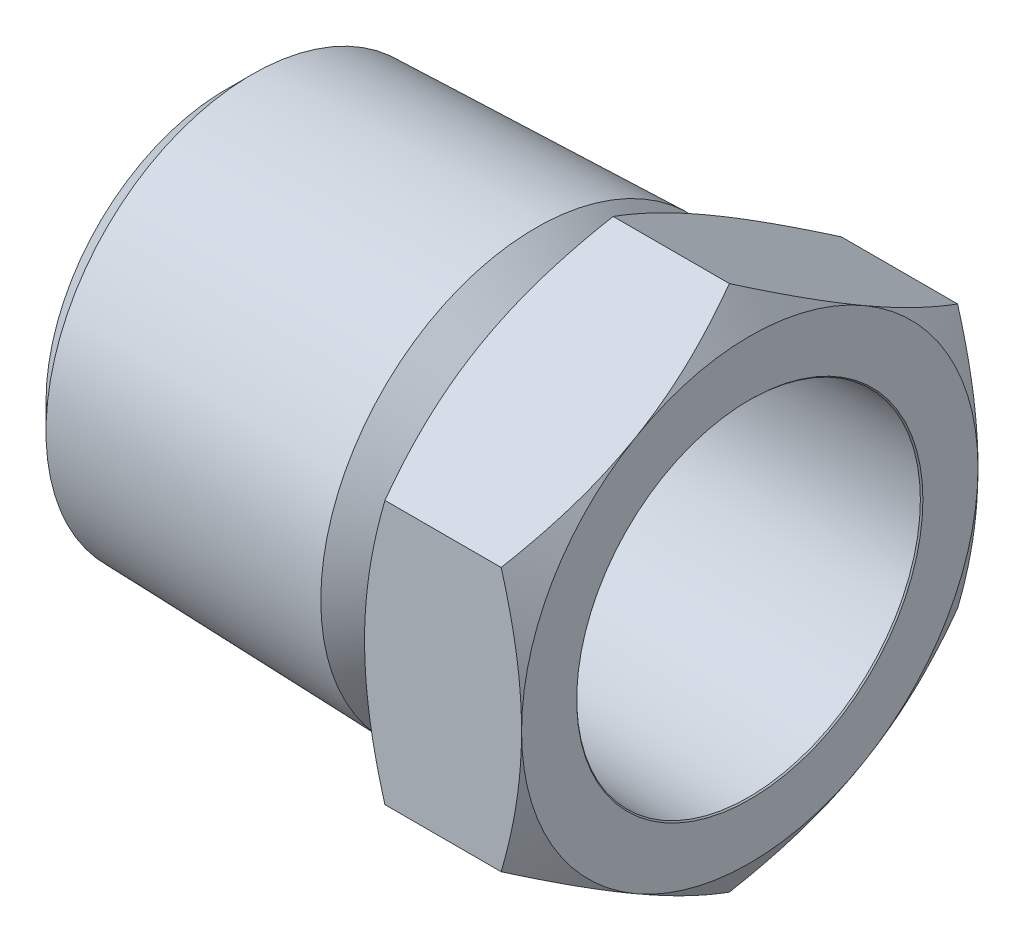
SolidWorks part; units mm, degrees
ref_plane "Front" through (0, 0, 0) normal (0, 0, 1) x (1, 0, 0)
ref_plane "Top" through (0, 0, 0) normal (0, 1, 0) x (1, 0, 0)
ref_plane "Right" through (0, 0, 0) normal (1, 0, 0) x (0, 0, -1)
sketch "Sketch1" plane through (0, 0, 0) normal (0, 0, 1) x (1, 0, 0)
  line L0 (-10.922, 0) -> (10.922, 0) construction
ref_plane "Plane1" through (-10.922, 0, 0) normal (1, 0, 0) x (0, 0, -1)
sketch "Sketch2" plane through (-10.922, 0, 0) normal (1, 0, 0) x (0, 0, -1)
  circle A0 centre (0, 0) radius 8.5725
  dimension "OD" = 17.145
extrude "Extrude1" add sketch "Sketch2" along normal up to vertex (21.844 mm away) draft 1.783 up to point (10.922, 0, 0) draft outward yes
sketch "Sketch3" plane through (-10.922, 0, 0) normal (-1, 0, 0) x (0, 0, 1)
  circle A1 centre (0, 0) radius 8.5725
  circle A2 centre (0, 0) radius 8.5725
  dimension "D1" = 0
curve "Helix/Spiral1" parameters "pitch"=1.4111
sketch "Sketch4" plane through (0, 0, 0) normal (0, 0, 1) x (1, 0, 0)
  line L0 (-12.1567, 8.5725) -> (-11.6276, 7.656)
  line L1 (-11.6276, 7.656) -> (-11.4512, 7.656)
  line L2 (-11.4512, 7.656) -> (-10.922, 8.5725)
  line L3 (-12.1567, 8.5725) -> (-10.922, 8.5725) construction
  line L4 (-11.8921, 8.1142) -> (-11.1866, 8.1142) construction
  line L5 (-11.5394, 7.656) -> (-11.5394, 8.5725) construction
  line L6 (-12.1567, 8.5725) -> (-10.7821, 8.8149)
  line L7 (-10.922, 8.5725) -> (-10.7821, 8.8149)
  line L8 (-10.922, 8.5725) -> (-10.922, -8.5725) construction
  dimension "D1" = 10
  dimension "D2" = 0.1764
  dimension "D3" = 0.7056
  dimension "D4" = 60
sweep "Cut-Sweep1" [suppressed] cut profiles "Sketch4" path "Helix/Spiral1"
sketch "Sketch5" plane through (-10.922, 0, 0) normal (1, 0, 0) x (0, 0, -1)
  circle A0 centre (0, 0) radius 7.656 construction
  circle A1 centre (0, 0) radius 7.529
  dimension "D1" = 0.127
extrude "Cut-Extrude1" cut sketch "Sketch5" along normal through all draft 45 flip side to cut
ref_plane "Plane2" through (10.922, 0, 0) normal (1, 0, 0) x (0, 0, -1)
ref_plane "Plane3" through (4.3688, 0, 0) normal (1, 0, 0) x (0, 0, -1)
sketch "Sketch8" plane through (4.3688, 0, 0) normal (1, 0, 0) x (0, 0, -1)
  circle A2 centre (0, 0) radius 14.9225
  circle A3 centre (0, 0) radius 14.9225
  dimension "D1" = 6.35
extrude "Cut-Extrude4" cut sketch "Sketch8" along normal through all
sketch "Sketch9" plane through (4.3688, 0, 0) normal (1, 0, 0) x (0, 0, -1)
  circle A0 centre (0, 0) radius 8.5725 construction
  circle A2 centre (0, 0) radius 7.656
extrude "Cut-Extrude5" cut sketch "Sketch9" against normal blind 1.0583 flip side to cut
ref_plane "Plane4" through (3.3105, 0, 0) normal (1, 0, 0) x (0, 0, -1)
sketch "Sketch10" plane through (3.3105, 0, 0) normal (1, 0, 0) x (0, 0, -1)
  circle A1 centre (0, 0) radius 7.656
  circle A2 centre (0, 0) radius 7.656
  dimension "D1" = 0
extrude "Cut-Extrude6" cut sketch "Sketch10" against normal through all draft 45 flip side to cut
sketch "Sketch6" plane through (10.922, 0, 0) normal (1, 0, 0) x (0, 0, -1)
  line L1 (0, 10.9985) -> (-9.525, 5.4993)
  line L2 (-9.525, 5.4993) -> (-9.525, -5.4993)
  line L3 (-9.525, -5.4993) -> (0, -10.9985)
  line L4 (0, -10.9985) -> (9.525, -5.4993)
  line L5 (9.525, -5.4993) -> (9.525, 5.4993)
  line L6 (9.525, 5.4993) -> (0, 10.9985)
  circle A0 centre (0, 0) radius 9.525 construction
  dimension "Hex" = 19.05
extrude "Extrude2" add sketch "Sketch6" against normal blind 6.5532
sketch "Sketch7" plane through (10.922, 0, 0) normal (1, 0, 0) x (0, 0, -1)
  line L0 (0, 10.9985) -> (-9.525, 5.4993) construction
  circle A0 centre (0, 0) radius 9.525
extrude "Cut-Extrude2" cut sketch "Sketch7" against normal through all draft 60 flip side to cut
sketch "Sketch18" plane through (4.3688, 0, 0) normal (-1, 0, 0) x (0, 0, 1)
  circle A0 centre (0, 0) radius 9.525 construction
  circle A1 centre (0, 0) radius 9.525
extrude "Extrude3" cut sketch "Sketch18" against normal blind 10 draft 60 flip side to cut
ref_plane "Plane5" through (0.762, 0, 0) normal (1, 0, 0) x (0, 0, -1)
sketch "Sketch11" plane through (0.762, 0, 0) normal (1, 0, 0) x (0, 0, -1)
  circle A0 centre (0, 0) radius 6.858
  dimension "OD2" = 13.716
extrude "Cut-Extrude7" cut sketch "Sketch11" along normal through all draft 1.783 draft outward yes
sketch "Sketch12" plane through (0.762, 0, 0) normal (1, 0, 0) x (0, 0, -1)
  circle A0 centre (0, 0) radius 6.858 construction
  circle A1 centre (0, 0) radius 6.858
curve "Helix/Spiral2" parameters "pitch 2"=1.4111
sketch "Sketch16" plane through (10.922, 0, 0) normal (1, 0, 0) x (0, 0, -1)
  circle A2 centre (0, 0) radius 7.2251
  circle A3 centre (0, 0) radius 7.2251
  dimension "D1" = 0.0508
sketch "Sketch14" plane through (0, 0, 0) normal (0, 0, 1) x (1, 0, 0)
  line L0 (-0.4727, 6.858) -> (0.762, 6.858) construction
  line L1 (0.762, 6.858) -> (0.2328, 5.9415) construction
  line L2 (0.2328, 5.9415) -> (0.0564, 5.9415)
  line L3 (0.0564, 5.9415) -> (-0.4727, 6.858)
  line L4 (-0.2081, 6.3997) -> (0.4974, 6.3997) construction
  line L5 (0.1446, 5.9415) -> (0.1446, 6.858) construction
  line L6 (-0.4727, 6.858) -> (0.9019, 7.1004)
  line L7 (0.9019, 7.1004) -> (0.2328, 5.9415)
  line L8 (0.762, -6.858) -> (0.762, 6.858) construction
  dimension "D1" = 10
  dimension "D2" = 60
  dimension "D3" = 0.1764
  dimension "D4" = 0.7056
sweep "Sweep1" [suppressed] add profiles "Sketch14" path "Helix/Spiral2"
sketch "Sketch15" plane through (10.922, 0, 0) normal (1, 0, 0) x (0, 0, -1)
  line L6 (0, 10.9985) -> (-9.525, 5.4993)
  line L7 (-9.525, 5.4993) -> (-9.525, -5.4993)
  line L8 (-9.525, -5.4993) -> (0, -10.9985)
  line L9 (0, -10.9985) -> (9.525, -5.4993)
  line L10 (9.525, -5.4993) -> (9.525, 5.4993)
  line L11 (9.525, 5.4993) -> (0, 10.9985)
  line L12 (0, 10.9985) -> (-9.525, 5.4993)
  line L13 (-9.525, 5.4993) -> (-9.525, -5.4993)
  line L14 (-9.525, -5.4993) -> (0, -10.9985)
  line L15 (0, -10.9985) -> (9.525, -5.4993)
  line L16 (9.525, -5.4993) -> (9.525, 5.4993)
  line L17 (9.525, 5.4993) -> (0, 10.9985)
  dimension "D1" = 0
extrude "Cut-Extrude8" [suppressed] cut sketch "Sketch15" along normal through all
extrude "Cut-Extrude9" cut sketch "Sketch16" against normal blind 6.35 draft 45
sketch "Sketch17" plane through (0, 0, 0) normal (0, 0, 1) x (1, 0, 0)
  line L1 (-10.922, 6.3997) -> (0.762, 6.3997)
  line L2 (0.762, 6.3997) -> (0.762, 0)
  line L3 (0.762, 0) -> (-10.922, 0)
  line L4 (-10.922, 0) -> (-10.922, 6.3997)
  line L5 (-10.922, -8.5725) -> (-10.922, 8.5725) construction
  line L6 (0.762, -6.858) -> (0.762, 6.858) construction
revolve "Cut-Revolve1" cut sketch "Sketch17" angle 360 about L0
equation "\"D3@Helix/Spiral1\" = \"L@Sketch1\""
equation "\"D2@Sketch4\" = \"pitch@Helix/Spiral1\"*.125"
equation "\"D3@Sketch4\" = \"pitch@Helix/Spiral1\"*.5"
equation "\"D1@Extrude2\" = \"L@Sketch1\"*.3"
equation "\"D1@Plane3\" = \"D1@Extrude2\""
equation "\"D1@Cut-Extrude5\" = \"pitch@Helix/Spiral1\"*.75"
equation "\"D1@Plane4\" = \"D1@Cut-Extrude5\""
equation "\"D3@Helix/Spiral2\" = \"thread engagement @Plane5\"+.250"
equation "\"D3@Sketch14\" = \"pitch 2@Helix/Spiral2\"*.125"
equation "\"D4@Sketch14\" = \"pitch 2@Helix/Spiral2\"*.50"
